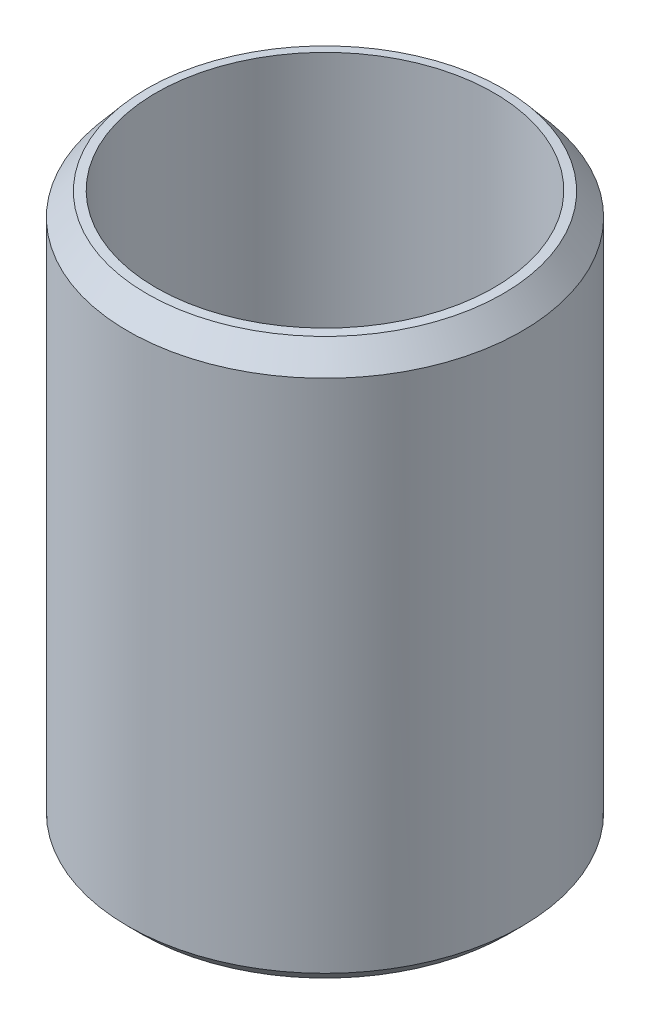
SolidWorks part; units mm, degrees
material "1.0037 (S235JR)"
ref_plane "Alzado" through (0, 0, 0) normal (0, 0, 1) x (1, 0, 0)
ref_plane "Planta" through (0, 0, 0) normal (0, 1, 0) x (1, 0, 0)
ref_plane "Vista lateral" through (0, 0, 0) normal (1, 0, 0) x (0, 0, -1)
sketch "Croquis1" plane through (0, 0, 0) normal (0, 0, 1) x (1, 0, 0)
  line L1 (-7, 18.8082) -> (-7, 0)
  line L2 (-7, 0) -> (0, 0)
  line L3 (0, 0) -> (0, 20)
  line L4 (-7, 18.8082) -> (-6, 20)
  line L5 (-6, 20) -> (0, 20)
  dimension "D1" = 7
  dimension "D2" = 130
  dimension "D3" = 6
  dimension "D4" = 20
revolve "Revolución1" add sketch "Croquis1" angle 360 about L3
sketch "Croquis2" plane through (0, 20, 0) normal (0, 1, 0) x (1, 0, 0)
  circle A0 centre (0, 0) radius 6
  dimension "D1" = 12
extrude "Cortar-Extruir1" cut sketch "Croquis2" against normal blind 60
chamfer "Chaflán2" distance 0.5 angle 45 3 edges at (0, 0, 6) (0, 0, -7) (0, 20, 6) first distance on face at (0, 20, 6) first distance on face at (0, 0, -7) first distance on face at (0, 18.8082, -7)
